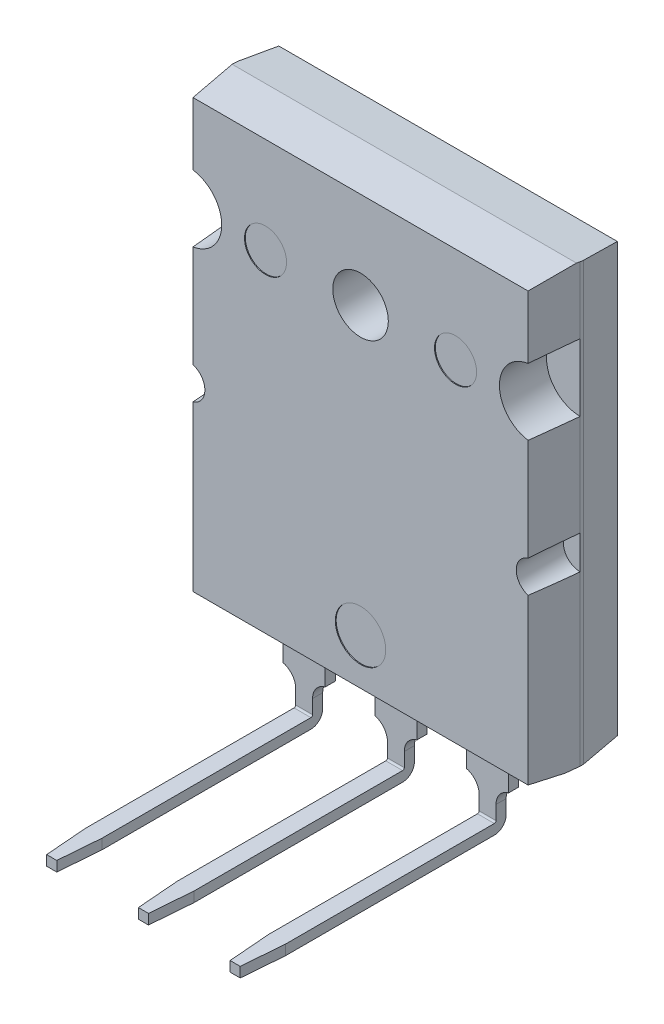
SolidWorks part; units mm, degrees
ref_plane "Płaszczyzna przednia" through (0, 0, 0) normal (0, 0, 1) x (1, 0, 0)
ref_plane "Płaszczyzna górna" through (0, 0, 0) normal (0, 1, 0) x (1, 0, 0)
ref_plane "Płaszczyzna prawa" through (0, 0, 0) normal (1, 0, 0) x (0, 0, -1)
sketch "Szkic1" plane through (0, 0, 0) normal (0, 0, 1) x (1, 0, 0)
  line L1 (-23.4326, 19.7455) -> (-2.9326, 19.7455)
  line L2 (-23.4326, 19.7455) -> (-23.4326, -6.2545)
  line L3 (-23.4326, -6.2545) -> (-2.9326, -6.2545)
  line L4 (-2.9326, 19.7455) -> (-2.9326, -6.2545)
  line L5 (-13.1826, 13.7455) -> (-13.1826, -11.2545) construction
  line L6 (-13.1826, -11.2545) -> (-15.7875, -11.2545) construction
  circle A0 centre (-13.1826, 13.7455) radius 1.65
  dimension "D3" = 3.3
  dimension "D1" = 20.5
  dimension "D2" = 26
  dimension "D4" = 6
extrude "Dodanie-wyciągnięcie1" add sketch "Szkic1" along normal blind 5.2
sketch "Szkic2" plane through (0, 0, 5.2) normal (0, 0, 1) x (1, 0, 0)
  line L0 (-23.4326, 19.7455) -> (-23.4326, -6.2545) construction
  line L1 (-13.1826, 19.7455) -> (-13.1826, -49980.2545) construction
  line L2 (-2.9326, 19.7455) -> (-23.4326, 19.7455) construction
  circle A0 centre (-23.4326, 13.7455) radius 2
  circle A1 centre (-2.9326, 13.7455) radius 2
  circle A2 centre (-23.4326, 4.7455) radius 1
  circle A3 centre (-2.9326, 4.7455) radius 1
  point P8 (-13.1826, 19.7455)
  dimension "D1" = 4
  dimension "D2" = 2
  dimension "D3" = 11
extrude "Wytnij-wyciągnięcie1" cut sketch "Szkic2" against normal blind 2.8
sketch "Szkic4" plane through (0, -6.2545, 0) normal (0, -1, 0) x (1, 0, 0)
  line L0 (-13.1826, 5.2) -> (-13.1826, -49994.8) construction
  line L1 (-14.4333, 3.1) -> (-11.9333, 3.1)
  line L2 (-14.4333, 3.1) -> (-14.4333, 2.5)
  line L3 (-14.4333, 2.5) -> (-11.9333, 2.5)
  line L4 (-11.9333, 3.1) -> (-11.9333, 2.5)
  line L5 (-23.4326, 5.2) -> (-2.9326, 5.2) construction
  line L6 (-14.4333, 2.5) -> (-11.9333, 3.1) construction
  line L7 (-11.9333, 2.5) -> (-14.4333, 3.1) construction
  line L8 (-14.4333, 2.8) -> (-11.9333, 2.8) construction
  line L9 (-23.4326, 0) -> (-2.9326, 0) construction
  point P8 (-13.1826, 5.2)
  dimension "D1" = 0.6
  dimension "D2" = 2.5
  dimension "D3" = 2.8
extrude "Dodanie-wyciągnięcie2" add sketch "Szkic4" along normal blind 2.8
sketch "Szkic7" plane through (0, -9.0545, 0) normal (0, -1, 0) x (1, 0, 0)
  line L0 (-11.9333, 3.1) -> (-14.4333, 3.1) construction
  line L1 (-13.6833, 3.1) -> (-12.6833, 3.1)
  line L2 (-13.6833, 3.1) -> (-13.6833, 2.5)
  line L3 (-13.6833, 2.5) -> (-12.6833, 2.5)
  line L4 (-12.6833, 3.1) -> (-12.6833, 2.5)
  line L5 (-13.1833, 3.1) -> (-13.1833, 2.5476) construction
  line L7 (-14.4333, 2.5) -> (-11.9333, 2.5) construction
  line L8 (-13.1833, 2.5) -> (-13.1833, 3.1) construction
  dimension "D1" = 1
extrude "Dodanie-wyciągnięcie3" add sketch "Szkic7" along normal blind 2.5
fillet "Zaokrąglenie2" radius 1 2 edges
sketch3d "Szkic 3D1"
  line L0 (-13.1826, -6.2545, 5.2) -> (-13.1826, -6.2545, -49994.8) construction
  line L1 (-23.4326, -6.2545, 5.2) -> (-2.9326, -6.2545, 5.2) construction
  line L3 (-23.4326, -6.2545, 0) -> (-2.9326, -6.2545, 0) construction
  point P4 (-13.1826, -6.2545, 5.2)
  point P10 (-13.1826, -6.2545, 0)
chamfer "Sfazowanie3" distance 2.2 angle 5 2 edges at (-23.4326, 6.7455, 0) (-2.9326, 6.7455, 0)
chamfer "Sfazowanie4" distance 2.8 angle 6 6 edges at (-2.9326, -1.2545, 5.2) (-2.9326, 8.7455, 5.2) (-2.9326, 17.7455, 5.2) (-23.4326, 17.7455, 5.2) (-23.4326, -1.2545, 5.2) (-23.4326, 8.7455, 5.2)
chamfer "Sfazowanie5" distance 2.8 angle 6 2 edges at (-13.1826, 19.7455, 0) (-13.1826, 19.7455, 5.2)
chamfer "Sfazowanie6" distance 2.2 angle 7 1 edges at (-13.1826, -6.2545, 0)
chamfer "Sfazowanie7" distance 2 angle 8 1 edges at (-13.1826, -6.2545, 5.2)
sketch "草图1" plane through (0, 0, 3.1) normal (0, 0, 1) x (1, 0, 0)
  line L0 (-13.6833, -11.5545) -> (-13.6833, -10.0227) construction
  line L1 (-13.6833, -10.9545) -> (-12.6833, -10.9545)
  line L2 (-13.6833, -10.9545) -> (-13.6833, -11.5545)
  line L3 (-13.6833, -11.5545) -> (-12.6833, -11.5545)
  line L4 (-12.6833, -10.9545) -> (-12.6833, -11.5545)
extrude "凸台-拉伸1" add sketch "草图1" along normal blind 15
fillet "圆角1" radius 0.1 1 edges at (-13.1833, -10.9545, 3.1)
fillet "圆角2" radius 0.7 1 edges at (-13.1833, -11.5545, 2.5)
chamfer "倒角1" distance 2.5 distance2 0.2 2 edges at (-13.6833, -11.2545, 18.1) (-12.6833, -11.2545, 18.1)
pattern_linear "阵列(线性)9" count 2 spacing 5.45 along (1, 0, 0) count 2 spacing 5.45 along (-1, 0, 0) of "Dodanie-wyciągnięcie2", "Dodanie-wyciągnięcie3", "Zaokrąglenie2", "凸台-拉伸1", "圆角1", "圆角2", "倒角1"
sketch "草图4" plane through (0, 0, 0) normal (0, 0, -1) x (-1, 0, 0)
  line L0 (5.7502, 17.9512) -> (4.1251, 16.3261)
  line L1 (13.1826, 13.7455) -> (0, 13.7455) construction
  line L2 (4.1251, 15.1686) -> (4.1251, 16.3261)
  line L3 (13.1826, 18.698) -> (13.1826, -7.9974) construction
  line L4 (4.1251, -1.3459) -> (4.2635, -1.4844)
  line L5 (5.7502, 17.9512) -> (20.6151, 17.9512)
  line L6 (4.1251, 12.3224) -> (4.1251, -1.3459)
  line L7 (4.2635, -1.4844) -> (22.1017, -1.4844)
  line L8 (20.6151, 17.9512) -> (22.2402, 16.3261)
  line L9 (22.2402, 15.1686) -> (22.2402, 16.3261)
  line L10 (22.2402, 12.3224) -> (22.2402, -1.3459)
  line L11 (22.2402, -1.3459) -> (22.1017, -1.4844)
  circle A0 centre (13.1826, 13.7455) radius 3.5
  arc A1 (4.1251, 12.3224) -> (4.1251, 15.1686) centre (3.5226, 13.7455) ccw
  arc A2 (22.2402, 12.3224) -> (22.2402, 15.1686) centre (22.8427, 13.7455) cw
  point P16 (13.1826, 17.9512)
  point P22 (13.1826, -1.4844)
  dimension "D5" = 7
extrude "凸台-拉伸3" add sketch "草图4" along normal blind 0.0001
sketch "草图5" plane through (0, 0, 5.2) normal (0, 0, 1) x (1, 0, 0)
  line L1 (-13.1826, 15.3955) -> (-13.1826, 12.0955) construction
  circle A0 centre (-7.5371, 13.7455) radius 1.2499
  circle A1 centre (-13.1826, 13.7455) radius 1.65 construction
  circle A2 centre (-18.8282, 13.7455) radius 1.2499
  circle A3 centre (-13.1826, -3.2456) radius 1.4973
extrude "切除-拉伸1" cut sketch "草图5" against normal blind 0.05
